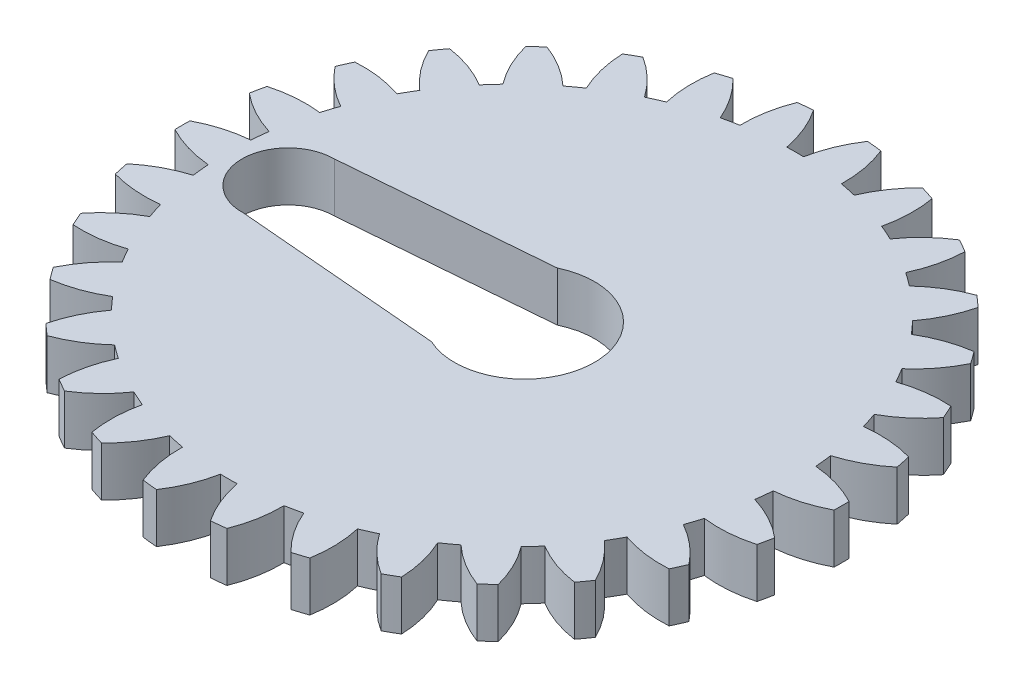
SolidWorks part; units mm, degrees
ref_plane "Front Plane" through (0, 0, 0) normal (0, 0, 1) x (1, 0, 0)
ref_plane "Top Plane" through (0, 0, 0) normal (0, 1, 0) x (1, 0, 0)
ref_plane "Right Plane" through (0, 0, 0) normal (1, 0, 0) x (0, 0, -1)
sketch "Sketch1" plane through (0, 0, 0) normal (0, 1, 0) x (1, 0, 0)
  circle A0 centre (0, 0) radius 20
  dimension "addendumDiamteter" = 40
extrude "Boss-Extrude1" add sketch "Sketch1" along normal blind 3
sketch "Sketch2" plane through (0, 3, 0) normal (0, 1, 0) x (1, 0, 0)
  line L0 (0, 0) -> (0, 28.8712) construction
  line L1 (0, 0) -> (-1.8095, 17.2166) construction
  line L3 (-0.9809, 18.7243) -> (-1.9572, 18.6217) construction
  circle A0 centre (0, 0) radius 18.75 construction
  circle A2 centre (0, 0) radius 17.1875 construction
  circle A3 centre (0, 0) radius 17.6192 construction
  arc A4 (-0.5066, 17.18) -> (0.5066, 17.18) centre (0, 0) cw
  arc A5 (-1.6375, 19.9329) -> (1.6375, 19.9329) centre (0, 0) cw
  circle A6 centre (0, 0) radius 20 construction
  arc A7 (-1.6375, 19.9329) -> (-0.5066, 17.18) centre (-7.8715, 15.7631) cw
  arc A8 (1.6375, 19.9329) -> (0.5066, 17.18) centre (7.8715, 15.7631) ccw
  dimension "dedendumCircle" = 34.375
  dimension "baseDiameter" = 35.2385
  dimension "PitchDiameter" = 37.5
  dimension "D1" = 7.5
  dimension "D4" = 6
  dimension "D2" = 0.9817
extrude "Cut-Extrude1" cut sketch "Sketch2" against normal through all
pattern_circular "CirPattern1" count 30 over 360 about axis through (0, 0, 0) along (0, 1, 0) of "Cut-Extrude1"
sketch "Sketch3" plane through (0, 3, 0) normal (0, 1, 0) x (1, 0, 0)
  line L0 (0, 2) -> (-4.1557, 9.9831)
  line L2 (4.1557, 9.9831) -> (0, 2)
  line L3 (0, 0) -> (0, 31.2074) construction
  line L4 (0, 0) -> (46.4667, 0) construction
  line L5 (-4.1557, 9.9831) -> (4.1557, 9.9831) construction
  arc A0 (-4.1557, 9.9831) -> (4.1557, 9.9831) centre (0, -1.2743) cw
  dimension "D4" = 12
  dimension "D1" = 55
  dimension "D2" = 2
  dimension "D3" = 9
extrude "Cut-Extrude2" [suppressed] cut sketch "Sketch3" against normal blind 10
fillet "Fillet1" [suppressed] radius 1
fillet "Fillet2" [suppressed] radius 1
fillet "Fillet3" [suppressed] radius 1
pattern_circular "CirPattern2" [suppressed] count 6 over 360 of bodies 104
sketch "Sketch6" plane through (0, 3, 0) normal (0, 1, 0) x (1, 0, 0)
  line L0 (0, 0) -> (22.423, 0) construction
  line L1 (22.423, 0) -> (0, 0) construction
  line L2 (0, 0) -> (0, 27.3259) construction
  line L3 (1.3229, 1.5) -> (-1.3229, 1.5)
  arc A0 (-1.3229, 1.5) -> (1.3229, 1.5) centre (0, 0) ccw
  dimension "D1" = 2
  dimension "D2" = 1.5
extrude "Cut-Extrude5" [suppressed] cut sketch "Sketch6" against normal through all
sketch "Sketch7" plane through (0, 3, 0) normal (0, 1, 0) x (1, 0, 0)
  line L0 (-13.6177, 2.8368) -> (-1.1177, 3.8664)
  line L1 (-13.5267, -2.7617) -> (-1.0715, -3.8186)
  line L2 (-1.1177, 3.8664) -> (-1.0715, -3.8186) construction
  line L3 (0, 13.327) -> (0.1498, -11.5733) construction
  arc A0 (-1.0715, -3.8186) -> (-1.1177, 3.8664) centre (0.7212, 0.0349) ccw
  arc A1 (-13.5267, -2.7617) -> (-13.6177, 2.8368) centre (-13.6177, 0.0368) cw
  dimension "D1" = 4.25
  dimension "D2" = 2.8
  dimension "D3" = 12.5
  dimension "D4" = 12.5
extrude "Cut-Extrude6" cut sketch "Sketch7" against normal blind 10
equation "\"module\" = 1.25"
equation "\"teeth\"= 30"
equation "\"pressureAngle\"= 20deg"
equation "\"gearThickness\"= 3"
equation "\"addendumFactor\"= 1"
equation "\"dedendumFactor\"= 1.25"
equation "\"pitch\"= 1 / \"module\""
equation "\"pitchDiameter\"= \"teeth\" / \"pitch\""
equation "\"addendum\"= \"addendumFactor\" / \"pitch\""
equation "\"dedendum\"= \"dedendumFactor\" / \"pitch\""
equation "\"addendumDiamteter@Sketch1\"=\"pitchDiameter\"+(\"addendum\"*2)"
equation "\"dedendumCircle@Sketch2\"=\"pitchDiameter\" -2 *\"dedendum\""
equation "\"baseDiameter@Sketch2\"=\"pitchDiameter\"*cos( \"pressureAngle\")"
equation "\"PitchDiameter@Sketch2\"=\"pitchDiameter\""
equation "\"D4@Sketch2\"=180/\"teeth\""
equation "\"D1@Sketch2\"=\"pitchDiameter\"/5"
equation "\"D2@Sketch2\"=PI / 2 / \"pitch\" / 2"
equation "\"D1@CirPattern1\"=\"teeth\""
